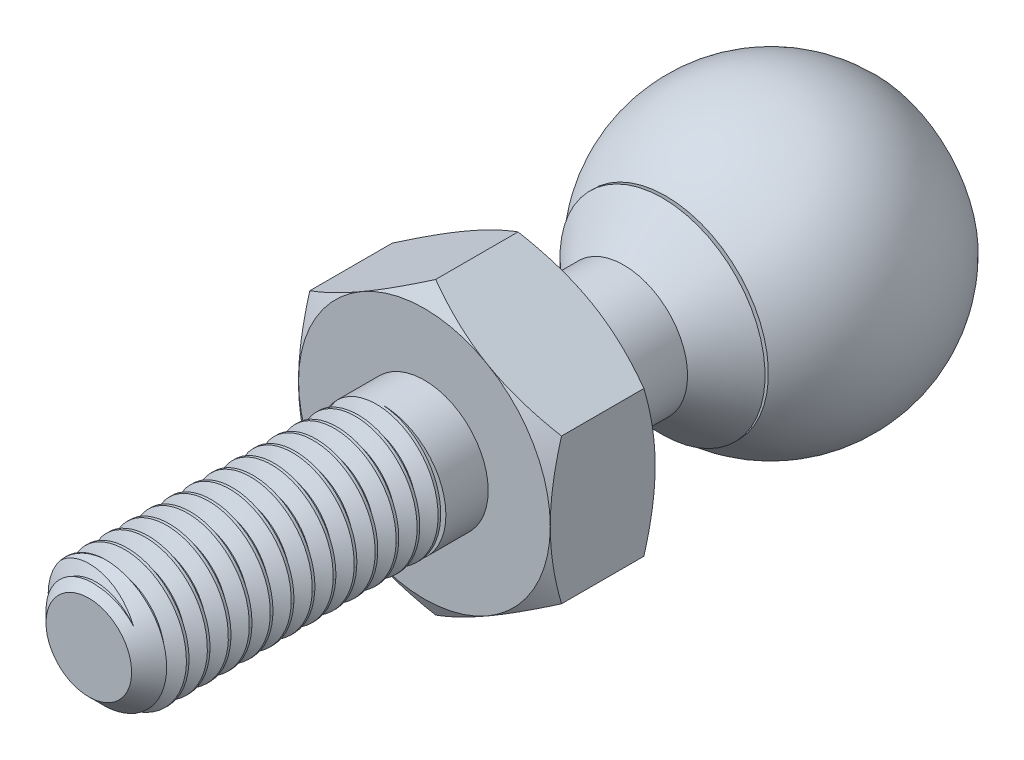
SolidWorks part; units mm, degrees
material "6061-T6 (SS)"
ref_plane "Front" through (0, 0, 0) normal (0, 0, 1) x (1, 0, 0)
ref_plane "Top" through (0, 0, 0) normal (0, 1, 0) x (1, 0, 0)
ref_plane "Right" through (0, 0, 0) normal (1, 0, 0) x (0, 0, -1)
sketch "Sketch1" plane through (0, 0, 0) normal (0, 0, 1) x (1, 0, 0)
  line L0 (0, 0) -> (0, -19.05)
  line L1 (0, -19.05) -> (2.413, -19.05)
  line L2 (2.413, -19.05) -> (2.413, 0)
  line L3 (2.413, 0) -> (0, 0)
  line L5 (0, 20.6375) -> (0, 0) construction
  line L6 (0, 20.6375) -> (7.9375, 20.6375) construction
  line L7 (7.9375, 20.6375) -> (7.9375, 12.7) construction
  line L8 (-2.413, -19.05) -> (-2.413, 0) construction
  arc A0 (5.4115, 6.8932) -> (0, 20.6375) centre (0, 12.7) ccw construction
  circle A1 centre (0, 12.7) radius 2.413 construction
  circle A2 centre (0, 12.7) radius 5.5499 construction
  circle A3 centre (0, 12.7) radius 5.6054 construction
  arc A4 (2.413, 0) -> (5.4115, 6.8932) centre (11.8355, 0) cw construction
  dimension "A" = 4.826
  dimension "Ball Dia" = 11.0998
  dimension "B" = 15.875
  dimension "D1" = 11.2108
  dimension "D" = 31.75
  dimension "E" = 19.05
  dimension "Thread Dia" = 4.826
sketch "Sketch4" plane through (0, 0, 0) normal (0, 0, 1) x (1, 0, 0)
  line L0 (2.413, 0) -> (0, 0) construction
  line L2 (0, 20.6375) -> (0, 0) construction
  line L3 (2.413, 0) -> (0, 0)
  line L5 (0, 20.6375) -> (0, 0)
  line L6 (0, 20.6375) -> (0, 23.1775) construction
  arc A0 (5.4115, 6.8932) -> (0, 20.6375) centre (0, 12.7) ccw construction
  arc A1 (5.4115, 6.8932) -> (0, 20.6375) centre (0, 12.7) ccw
  arc A2 (5.4115, 6.8932) -> (2.413, 0) centre (11.8355, 0) ccw construction
  arc A3 (5.4115, 6.8932) -> (2.413, 0) centre (11.8355, 0) ccw
  dimension "D1" = 2.54
sketch "Sketch6" plane through (0, 0, 0) normal (0, 0, 1) x (1, 0, 0)
  circle A0 centre (0, 12.7) radius 5.6054 construction
  circle A1 centre (0, 12.7) radius 5.6054
sketch "Sketch7" plane through (0, 0, 0) normal (0, 0, 1) x (1, 0, 0)
  line L0 (0, 18.2499) -> (0, 7.1501)
  line L1 (0, 20.6375) -> (0, 0) construction
  line L2 (0, 0) -> (0, 7.1501) construction
  arc A0 (0, 7.1501) -> (0, 18.2499) centre (0, 12.7) ccw
  circle A1 centre (0, 12.7) radius 5.5499 construction
revolve "Revolve3" add sketch "Sketch7" angle 360 about L2
sketch "Sketch8" plane through (0, 0, 0) normal (1, 0, 0) x (0, 0, -1)
  line L1 (-3.9688, 18.2499) -> (3.9688, 18.2499) construction
  line L2 (-3.9688, 18.2499) -> (-3.9688, 0)
  line L3 (-3.9688, 0) -> (3.9688, 0) construction
  line L4 (3.9688, 18.2499) -> (3.9688, 0)
  line L5 (3.9688, 18.2499) -> (5.5499, 18.2499)
  line L6 (5.5499, 18.2499) -> (5.5499, 0)
  line L7 (5.5499, 0) -> (3.9688, 0)
  line L8 (-3.9688, 0) -> (-5.5499, 0)
  line L9 (-5.5499, 0) -> (-5.5499, 18.2499)
  line L10 (-5.5499, 18.2499) -> (-3.9688, 18.2499)
  circle A0 centre (0, 12.7) radius 5.5499 construction
  dimension "C" = 7.9375
extrude "Cut-Extrude3" cut sketch "Sketch8" against normal through all and the other way through all
sketch "Sketch10" plane through (0, 0, 0) normal (0, 0, 1) x (1, 0, 0)
  circle A0 centre (0, 12.7) radius 2.413 construction
  circle A1 centre (0, 12.7) radius 2.413
extrude "Cut-Extrude4" cut sketch "Sketch10" against normal through all and the other way through all
chamfer "Chamfer1" distance 0.2413 angle 45 2 edges at (2.413, 12.7, -3.9688) (2.413, 12.7, 3.9688)
sketch "Sketch12" plane through (0, 0, 0) normal (1, 0, 0) x (0, 0, -1)
  line L1 (3.9688, 12.7) -> (-25.8064, 12.7) construction
  line L2 (3.9688, 12.7) -> (3.9688, 15.113) construction
  line L3 (-14.7066, 15.113) -> (3.9688, 15.113) construction
  line L4 (-25.8064, 12.7) -> (-25.8064, 15.113)
  line L5 (3.9688, 8.8205) -> (3.9688, 16.5795) construction
  line L6 (3.9688, 12.7) -> (6.3818, 12.7) construction
  line L14 (0, 15.113) -> (0, 12.7) construction
  line L15 (0, 20.6375) -> (0, 0) construction
  line L20 (3.9688, 10.287) -> (-25.8064, 10.287) construction
  line L21 (-14.7066, 15.113) -> (-14.7066, 10.287) construction
  line L22 (-13.1064, 15.113) -> (-13.1064, 10.287) construction
  line L23 (-14.7066, 15.113) -> (-14.7066, 12.7)
  line L24 (-14.7066, 15.113) -> (-25.8064, 15.113)
  line L25 (-14.7066, 12.7) -> (-25.8064, 12.7)
  dimension "L Length" = 25.8064
  dimension "S Thread Length" = 11.0998
  dimension "P Length" = 12.7
revolve "Revolve4" add sketch "Sketch12" angle 360 about L6
chamfer "Chamfer3" distance 0.7937 angle 45 1 edges at (2.413, 12.7, 25.8064)
sketch "Sketch23" plane through (0, 0, 14.7066) normal (0, 0, -1) x (-1, 0, 0)
  circle A1 centre (0, 12.7) radius 2.413
  circle A2 centre (0, 12.7) radius 2.413
  dimension "D1" = 0
curve "Helix/Spiral3" pitch 0.7937 height 16.1798 turns 20.384
sketch "Sketch24" plane through (0, 0, 0) normal (1, 0, 0) x (0, 0, -1)
  line L0 (-14.7066, 15.113) -> (-14.0121, 15.113)
  line L1 (-14.0121, 15.113) -> (-14.3097, 14.5974)
  line L2 (-14.3097, 14.5974) -> (-14.4089, 14.5974)
  line L3 (-14.4089, 14.5974) -> (-14.7066, 15.113)
  line L4 (-14.5578, 14.8552) -> (-14.1609, 14.8552) construction
  dimension "D1" = 60
  dimension "D2" = 0.3969
  dimension "D3" = 0.0992
sweep "Cut-Sweep2" cut profiles "Sketch24" path "Helix/Spiral3" align with end faces yes
sketch "Sketch15" plane through (0, 0, 0) normal (1, 0, 0) x (0, 0, -1)
  line L0 (3.9688, 12.7) -> (6.3818, 12.7) construction
  line L1 (-14.7066, 12.7) -> (3.9688, 12.7)
  line L2 (-14.7066, 12.7) -> (-14.7066, 15.113)
  line L3 (-14.7066, 15.113) -> (3.9688, 15.113)
  line L4 (3.9688, 12.7) -> (3.9688, 15.113)
  line L5 (3.9688, 12.7) -> (6.3818, 12.7) construction
revolve "Revolve5" add sketch "Sketch15" angle 360 about L5
ref_plane "Plane1" through (0, 0, 13.1064) normal (0, 0, 1) x (1, 0, 0)
sketch "Sketch16" plane through (0, 0, 13.1064) normal (0, 0, 1) x (1, 0, 0)
  line L1 (0, 18.1993) -> (-4.7625, 15.4496)
  line L2 (-4.7625, 15.4496) -> (-4.7625, 9.9504)
  line L3 (-4.7625, 9.9504) -> (0, 7.2007)
  line L4 (0, 7.2007) -> (4.7625, 9.9504)
  line L5 (4.7625, 9.9504) -> (4.7625, 15.4496)
  line L6 (4.7625, 15.4496) -> (0, 18.1993)
  circle A0 centre (0, 12.7) radius 4.7625 construction
  dimension "D1" = 9.525
extrude "Extrude1" add sketch "Sketch16" against normal blind 3.9688
sketch "Sketch17" plane through (0, 0, 13.1064) normal (0, 0, 1) x (1, 0, 0)
  circle A0 centre (0, 12.7) radius 4.7625 construction
  circle A1 centre (0, 12.7) radius 4.7625
extrude "Cut-Extrude5" cut sketch "Sketch17" against normal through all draft 60 flip side to cut
sketch "Sketch18" plane through (0, 0, 9.1377) normal (0, 0, -1) x (-1, 0, 0)
  circle A0 centre (0, 12.7) radius 4.7625 construction
  circle A1 centre (0, 12.7) radius 4.7625
extrude "Cut-Extrude6" cut sketch "Sketch18" against normal through all draft 60 flip side to cut
sketch "Sketch20" plane through (0, 0, 0) normal (1, 0, 0) x (0, 0, -1)
  line L0 (-4.0958, 16.5795) -> (-5.5622, 15.113)
  line L1 (-5.5622, 15.113) -> (-4.0958, 15.113)
  line L2 (-4.0958, 15.113) -> (-4.0958, 16.5795)
  line L3 (-14.7066, 15.113) -> (3.9688, 15.113) construction
  line L4 (-3.9688, 16.5795) -> (-4.0958, 16.5795) construction
  line L6 (-3.9688, 16.5795) -> (-3.9688, 8.8205) construction
  line L7 (3.9688, 12.7) -> (-25.8064, 12.7) construction
  line L8 (3.9688, 12.7) -> (-25.8064, 12.7) construction
  arc A0 (3.9688, 16.5795) -> (-3.9687, 16.5795) centre (0, 12.7) ccw construction
  dimension "D1" = 0.127
  dimension "D2" = 45
revolve "Revolve6" add sketch "Sketch20" angle 360 about L8
sketch "Sketch11" plane through (0, 0, 0) normal (1, 0, 0) x (0, 0, -1)
  line L0 (0, 12.7) -> (-3.9688, 14.3439) construction
  line L2 (0, 12.7) -> (-3.9688, 11.0561) construction
  line L4 (-3.9688, 18.2499) -> (-3.9688, 0) construction
  line L5 (0, 12.7) -> (0.4693, 12.8944) construction
  line L7 (0.4693, 12.5056) -> (0, 12.7) construction
  arc A0 (3.9688, 16.5795) -> (-3.9688, 16.5795) centre (0, 12.7) ccw construction
  dimension "D1" = 0.508
  dimension "Swivel" = 45
equation "\"D1@Sketch1\"=\"Ball Dia@Sketch1\"*1.01"
equation "\"D1@Chamfer1\"=\"A@Sketch1\"/20"
equation "\"D1@Extrude1\"= \"D4@Helix/Spiral3\" * 5"
equation "\"D3@Helix/Spiral3\" = \"S Thread Length@Sketch12\" + .2"
equation "\"D3@Sketch24\" = \"D4@Helix/Spiral3\" * .125"
equation "\"D2@Sketch24\" = \"D4@Helix/Spiral3\" * .5"
equation "\"D1@Chamfer3\" = \"D4@Helix/Spiral3\" * 1"
